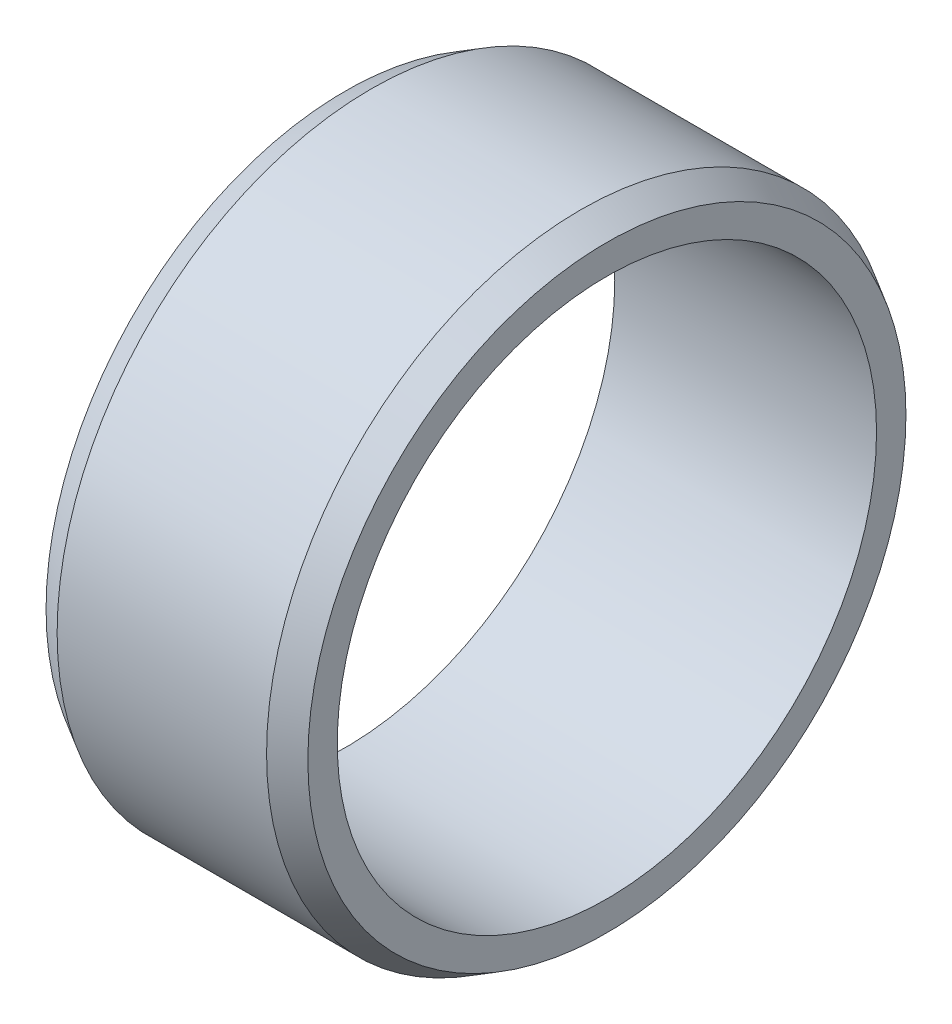
SolidWorks part; units mm, degrees
ref_plane "Front Plane" through (0, 0, 0) normal (0, 0, 1) x (1, 0, 0)
ref_plane "Top Plane" through (0, 0, 0) normal (0, 1, 0) x (1, 0, 0)
ref_plane "Right Plane" through (0, 0, 0) normal (1, 0, 0) x (0, 0, -1)
sketch "Sketch1" plane through (0, 0, 0) normal (0, 0, 1) x (1, 0, 0)
  line L0 (0, 5.15) -> (5, 5.15)
  line L1 (5, 5.15) -> (5, 5.7113)
  line L2 (5, 5.7113) -> (4.5, 6)
  line L3 (4.5, 6) -> (0.5, 6)
  line L4 (0.5, 6) -> (0, 5.7113)
  line L5 (0, 5.7113) -> (0, 5.15)
  line L6 (5, 0) -> (0, 0) construction
revolve "Revolve1" add sketch "Sketch1" angle 360 about L6
ref_plane "Plane1" through (5, 0, 0) normal (1, 0, 0) x (0, 0, -1)
ref_plane "anbau XY" through (0, 0, 0) normal (1, 0, 0) x (0, 0, -1)
ref_plane "anbau XZ" through (0, 0, 0) normal (0, -1, 0) x (-1, 0, 0)
ref_plane "anbau YZ" through (0, 0, 0) normal (0, 0, -1) x (-1, 0, 0)
ref_axis "anbau X" through (0, 0, 80.9) along (0, 0, -1)
ref_axis "anbau Y" through (0, -50, 0) along (0, 1, 0)
ref_axis "anbau Z" through (80.9, 0, 0) along (-1, 0, 0)
sketch3d "anbau"
  point P0 (0, 0, 0)
ref_plane "insert XY" through (0, 0, 0) normal (1, 0, 0) x (0, 0, -1)
ref_plane "insert XZ" through (0, 0, 0) normal (0, -1, 0) x (-1, 0, 0)
ref_plane "insert YZ" through (0, 0, 0) normal (0, 0, -1) x (-1, 0, 0)
ref_axis "insert X" through (0, 0, 80.9) along (0, 0, -1)
ref_axis "insert Y" through (0, -50, 0) along (0, 1, 0)
ref_axis "insert Z" through (80.9, 0, 0) along (-1, 0, 0)
sketch3d "insert"
  point P0 (0, 0, 0)
ref_plane "schraube_punkt XY" through (5, 0, 0) normal (1, 0, 0) x (0, 0, -1)
ref_plane "schraube_punkt XZ" through (0, 0, 0) normal (0, -1, 0) x (-1, 0, 0)
ref_plane "schraube_punkt YZ" through (0, 0, 0) normal (0, 0, -1) x (-1, 0, 0)
ref_axis "schraube_punkt X" through (5, 0, 80.9) along (0, 0, -1)
ref_axis "schraube_punkt Y" through (5, -50, 0) along (0, 1, 0)
ref_axis "schraube_punkt Z" through (80.9, 0, 0) along (-1, 0, 0)
sketch3d "schraube_punkt"
  point P0 (5, 0, 0)
other "Freeze***"
